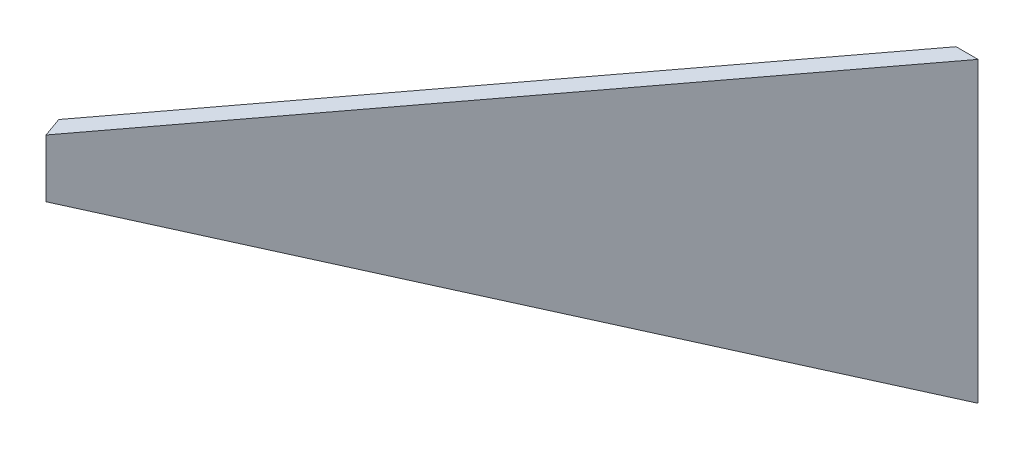
SolidWorks part; units mm, degrees
ref_plane "Front Plane" through (0, 0, 0) normal (0, 0, 1) x (1, 0, 0)
ref_plane "Top Plane" through (0, 0, 0) normal (0, 1, 0) x (1, 0, 0)
ref_plane "Right Plane" through (0, 0, 0) normal (1, 0, 0) x (0, 0, -1)
sketch "Sketch2" plane through (0, 0, 0) normal (0, 1, 0) x (1, 0, 0)
  line L0 (-57.15, 0) -> (224.536, 0)
  line L1 (224.536, 0) -> (-24.3577, -196.7539)
  line L2 (-24.3577, -196.7539) -> (-57.15, 0)
  line L3 (0, 0) -> (0, -152.4) construction
  line L4 (-31.75, -152.4) -> (31.75, -152.4) construction
  point P2 (0, 0)
  dimension "D1" = 281.686
  dimension "D2" = 57.15
  dimension "D3" = 63.5
  dimension "D4" = 152.4
extrude "Boss-Extrude1" add sketch "Sketch2" along normal blind 152.4
ref_plane "Plane1" through (-63.5, 0, 0) normal (1, 0, 0) x (0, 0, -1)
sketch "Sketch3" plane through (-63.5, 0, 0) normal (1, 0, 0) x (0, 0, -1)
  line L0 (0, 76.2) -> (-152.4, 76.2) construction
  line L1 (0, 152.4) -> (0, 0) construction
  line L2 (-152.4, 44.45) -> (-152.4, 107.95) construction
  line L3 (0, 152.4) -> (-152.4, 107.95)
  line L4 (0, 0) -> (-152.4, 44.45)
  line L5 (-152.4, 107.95) -> (-261.2571, 76.2)
  line L6 (-152.4, 44.45) -> (-261.2571, 76.2)
  line L7 (0, 152.4) -> (0, 0)
  point P7 (-152.4, 76.2)
  dimension "D1" = 152.4
  dimension "D2" = 63.5
extrude "Cut-Extrude2" cut sketch "Sketch3" along normal through all flip side to cut
shell "Shell1" thickness 6.35 removed face at (83.693, 76.2, 0)
sketch "Sketch4" plane through (-63.5, 0, 0) normal (1, 0, 0) x (0, 0, -1)
  line L1 (0, 152.4) -> (0, 145.7854)
  line L2 (0, 145.7854) -> (-196.7539, 88.3989)
  line L4 (-196.7539, 64.0011) -> (0, 6.6146)
  line L5 (0, 152.4) -> (-196.7539, 95.0134)
  line L7 (-196.7539, 57.3866) -> (0, 0)
  line L8 (-196.7539, 95.0134) -> (-196.7539, 57.3866) construction
  line L9 (-196.7539, 95.0134) -> (-196.7539, 88.3989)
  line L10 (-196.7539, 64.0011) -> (-196.7539, 57.3866)
  line L11 (0, 152.4) -> (0, 0) construction
  line L12 (0, 0) -> (0, 6.6146)
extrude "Cut-Extrude3" cut sketch "Sketch4" along normal through all
ref_plane "Plane2" through (0, 149.86, 0) normal (0, 1, 0) x (1, 0, 0)
sketch "Sketch5" plane through (0, 149.86, 0) normal (0, 1, 0) x (1, 0, 0)
  line L0 (-19.8615, -185.1052) -> (-18.6695, -192.2573)
  line L1 (-24.3577, -196.7539) -> (224.536, 0) construction
  line L2 (-19.8615, -185.1052) -> (-50.7124, 0) construction
  line L3 (-18.6695, -192.2573) -> (344.3171, -192.2573)
  line L4 (344.3171, -192.2573) -> (317.8797, 72.8643)
  line L5 (317.8797, 72.8643) -> (-35.1367, 43.3166)
  line L6 (-35.1367, 43.3166) -> (-19.8615, -185.1052)
extrude "Cut-Extrude4" cut sketch "Sketch5" against normal through all flip side to cut
